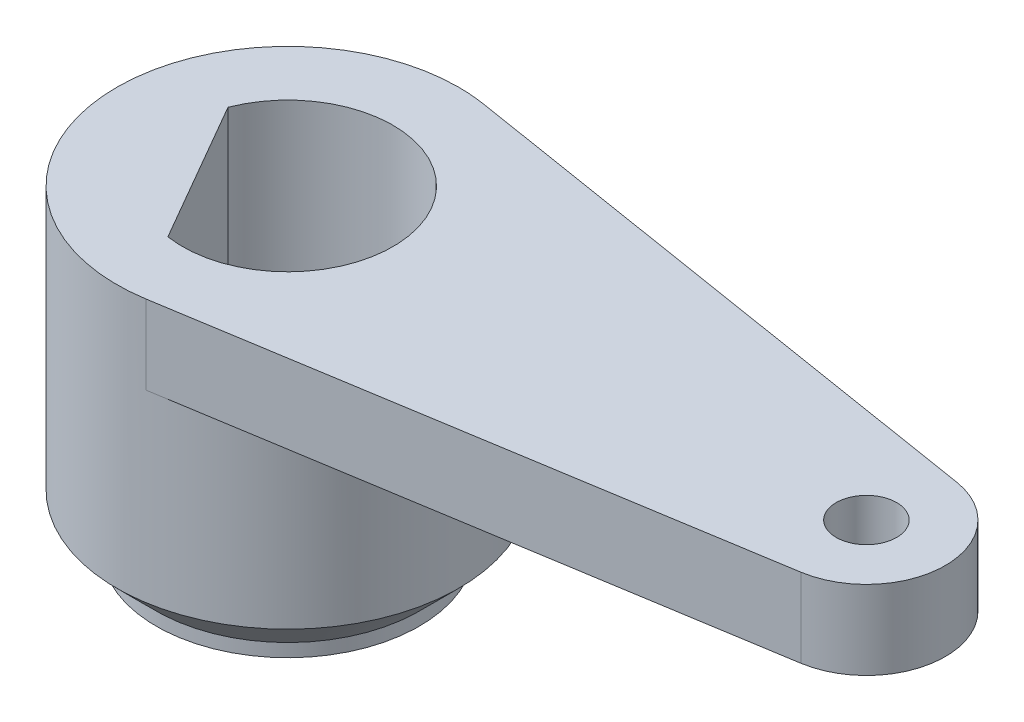
SolidWorks part; units mm, degrees
ref_plane "Front Plane" through (0, 0, 0) normal (0, 0, 1) x (1, 0, 0)
ref_plane "Top Plane" through (0, 0, 0) normal (0, 1, 0) x (1, 0, 0)
ref_plane "Right Plane" through (0, 0, 0) normal (1, 0, 0) x (0, 0, -1)
sketch "Sketch1" plane through (0, 0, 0) normal (0, 1, 0) x (1, 0, 0)
  circle A0 centre (0, 0) radius 4
  circle A2 centre (0, 0) radius 6.5
  dimension "D1" = 8
  dimension "D2" = 2.5
extrude "Boss-Extrude1" add sketch "Sketch1" along normal blind 12
sketch "Sketch2" plane through (0, 12, 0) normal (0, 1, 0) x (1, 0, 0)
  line L0 (1.0341, 6.4172) -> (22.4773, 2.9618)
  line L1 (1.0341, -6.4172) -> (22.4773, -2.9618)
  line L2 (0, 0) -> (22, 0) construction
  arc A0 (22.4773, -2.9618) -> (22.4773, 2.9618) centre (22, 0) ccw
  circle A1 centre (0, 0) radius 6.5 construction
  circle A2 centre (0, 0) radius 6.5
  circle A3 centre (22, 0) radius 1.15
  circle M6 centre (0, 0) radius 6.5
  dimension "D2" = 6
  dimension "D3" = 2.3
  dimension "D1" = 22
extrude "Boss-Extrude2" add sketch "Sketch2" against normal blind 3 contours L1 A0 L0 A2 M6 region at (13.5088, 12, 0)
sketch "Sketch4" plane through (0, 0, 0) normal (0, -1, 0) x (1, 0, 0)
  circle A0 centre (0, 0) radius 4 construction
  circle A1 centre (0, 0) radius 4
  circle A2 centre (0, 0) radius 5
  circle A3 centre (0, 0) radius 6.5 construction
  circle A4 centre (0, 0) radius 6.5
  circle M4 centre (0, 0) radius 6.5
  dimension "D1" = 1
extrude "Cut-Extrude1" cut sketch "Sketch4" against normal blind 2 contours A2 M4 region at (-6.3162, 0, 0)
sketch "Sketch5" plane through (0, 12, 0) normal (0, 1, 0) x (1, 0, 0)
  line L0 (-3.7263, 1.4542) -> (-0.6038, -3.9542)
  line L1 (-2.1651, -1.25) -> (0, 0) construction
  line L2 (0, 0) -> (-4, 0) construction
  circle A0 centre (0, 0) radius 4 construction
  circle A1 centre (0, 0) radius 4
  point P7 (-2.1566, -1.2645)
  circle M6 centre (0, 0) radius 4
  dimension "D1" = 2.5
  dimension "D2" = 30
extrude "Boss-Extrude4" add sketch "Sketch5" against normal blind 10 contours L0 M6 region at (-2.6941, 12, 1.5554)
chamfer "Chamfer1" distance 1.5 angle 45 1 edges at (0, 2, -5)
